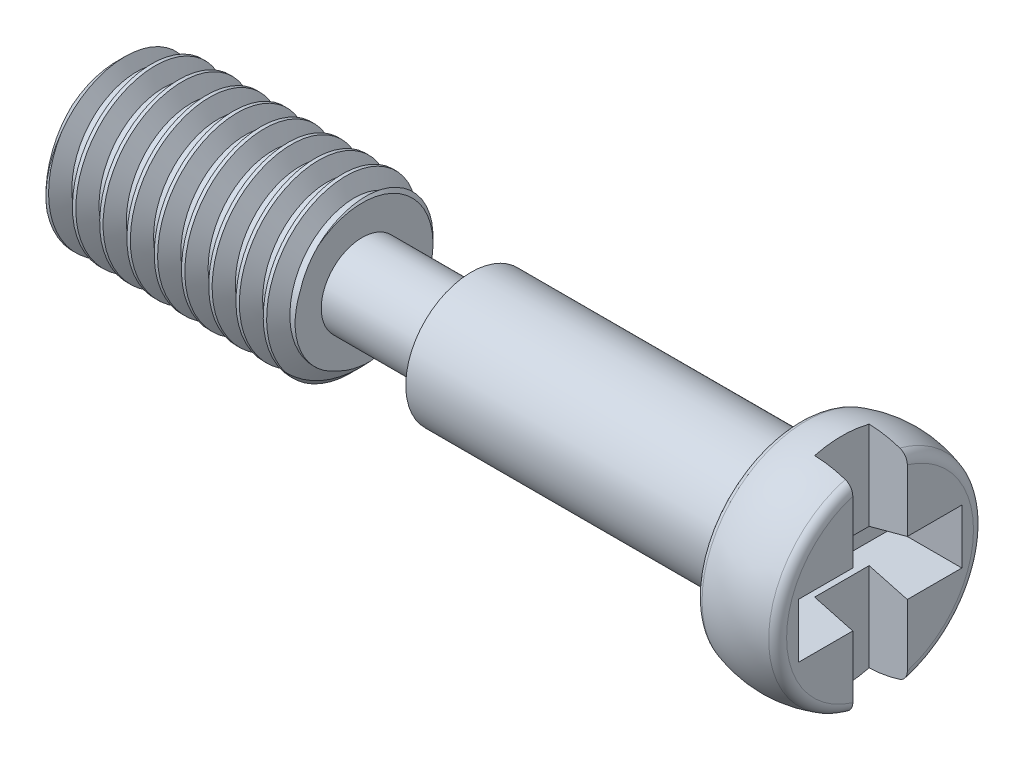
SolidWorks part; units mm, degrees
ref_plane "Front Plane" through (0, 0, 0) normal (0, 0, 1) x (1, 0, 0)
ref_plane "Top Plane" through (0, 0, 0) normal (0, 1, 0) x (1, 0, 0)
ref_plane "Right Plane" through (0, 0, 0) normal (1, 0, 0) x (0, 0, -1)
sketch "Sketch1" plane through (0, 0, 0) normal (0, 0, 1) x (1, 0, 0)
  line L0 (0, 0) -> (-2.0301, 0) construction
  line L1 (0, 0) -> (0, 1.3)
  line L2 (0.2, 1.5) -> (4.3, 1.5)
  line L3 (4.5, 1.3) -> (4.5, 0.75)
  line L4 (4.5, 0.75) -> (6.5, 0.75)
  line L5 (6.5, 0.75) -> (6.5, 1.2)
  line L6 (6.5, 1.2) -> (12.5, 1.2)
  line L7 (12.5, 1.2) -> (12.5, 1.7139)
  line L8 (0, 1.3) -> (0.2, 1.5)
  line L9 (14, 1.7139) -> (14, 0)
  line L10 (14, 0) -> (0, 0)
  line L11 (4.3, 1.5) -> (4.5, 1.3)
  arc A0 (12.6389, 1.9043) -> (13.8611, 1.9043) centre (13.25, 0) cw
  arc A1 (13.8611, 1.9043) -> (14, 1.7139) centre (13.8, 1.7139) cw
  arc A2 (12.6389, 1.9043) -> (12.5, 1.7139) centre (12.7, 1.7139) ccw
  point P4 (0, 1.5)
  point P5 (4.5, 1.5)
  point P10 (13.25, 2)
  point P15 (14, 2)
  point P18 (12.5, 2)
  dimension "D6" = 4
  dimension "D7" = 2
  dimension "D10" = 0.2
  dimension "D1" = 1.5
  dimension "D2" = 14
  dimension "D3" = 2.4
  dimension "D4" = 1.5
  dimension "D5" = 3
  dimension "D8" = 4.5
  dimension "D9" = 7.5
revolve "Body" add sketch "Sketch1" angle 360 about L0
thread "M3Thread" pitch 0.5 method cut profile "Thread Profile1" start angle 0, offset 1, length 6, pitch 0.5, diameter 3
ref_plane "Plane1" through (-1, 0, -1.5) normal (0, -1, 0) x (0, 0, -1)
sketch "Thread Profile1" plane through (-1, 0, -1.5) normal (0, -1, 0) x (0, 0, -1)
  line L0 (0, 0) -> (0, 0.5) construction
  line L11 (0, 0) -> (0, 0.4375)
  line L12 (0, 0.4375) -> (-0.2706, 0.2812)
  line L13 (-0.2706, 0.2812) -> (-0.2706, 0.1562)
  line L15 (-0.2706, 0.1562) -> (0, 0)
  line L17 (-0.2706, 0.2187) -> (0, 0.2187) construction
  point P2 (0, 0)
  dimension "Pitch" = 0.5
  dimension "Profile_Angle" = 60
  dimension "Profile_Land" = 0.125
  dimension "Profile_Height" = 0.2706
sketch "Sketch2" plane through (14, 0, 0) normal (1, 0, 0) x (0, 0, -1)
  line L0 (0, 0.8371) -> (0, 0) construction
  line L1 (0, 0) -> (0.9589, 0) construction
  line L3 (0.5, -2.064) -> (-0.5, -2.064)
  line L4 (0.5, -2.064) -> (0.5, 2.064)
  line L5 (0.5, 2.064) -> (-0.5, 2.064)
  line L6 (-0.5, -2.064) -> (-0.5, 2.064)
  line L7 (0.5, -2.064) -> (-0.5, 2.064) construction
  line L8 (0.5, 2.064) -> (-0.5, -2.064) construction
  line L9 (1.5, 0.5) -> (-1.5, 0.5)
  line L10 (1.5, 0.5) -> (1.5, -0.5)
  line L11 (1.5, -0.5) -> (-1.5, -0.5)
  line L12 (-1.5, 0.5) -> (-1.5, -0.5)
  line L13 (1.5, 0.5) -> (-1.5, -0.5) construction
  line L14 (1.5, -0.5) -> (-1.5, 0.5) construction
  circle M4 centre (0, 0) radius 1.7139
  dimension "D1" = 3
  dimension "D2" = 1
  dimension "D3" = 1
extrude "Cut-Extrude1" cut sketch "Sketch2" against normal blind 1 draft 15 contours L9 L12 L11 L6 | L11 L4 L9 L6 | L11 L10 L9 L4 region at (14, 0, 0) region at (14, 0, -1) region at (14, 0, 1)
extrude "Cut-Extrude2" cut sketch "Sketch2<3>" against normal blind 0.7 contours L9 L4 L6 M4 | L11 L4 L9 L6 | L4 L11 L6 M4 | L6 L4 L5 M4 | L6 L3 L4 M4 region at (14, -1.876, 0) region at (14, -1.0948, 0) region at (14, 0, 0) region at (14, 1.0948, 0) region at (14, 1.876, 0)
sketch "Sketch2<3>" plane through (14, 0, 0) normal (1, 0, 0) x (0, 0, -1) same geometry as "Sketch2"
